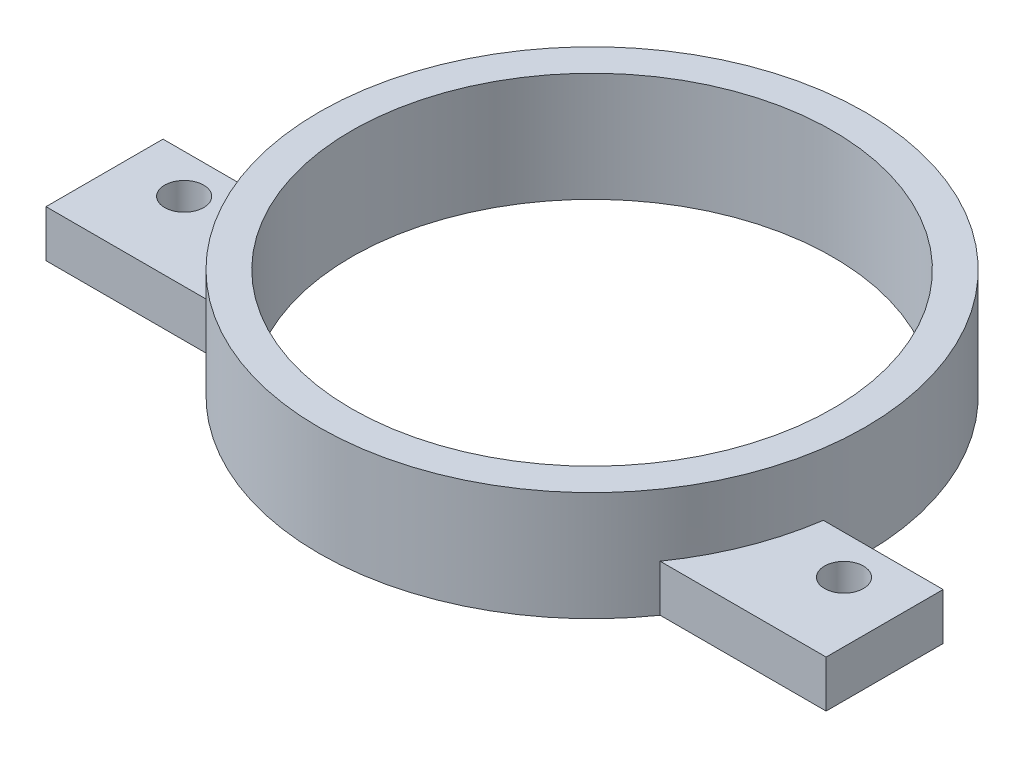
SolidWorks part; units mm, degrees
ref_plane "前视基准面" through (0, 0, 0) normal (0, 0, 1) x (1, 0, 0)
ref_plane "上视基准面" through (0, 0, 0) normal (0, 1, 0) x (1, 0, 0)
ref_plane "右视基准面" through (0, 0, 0) normal (1, 0, 0) x (0, 0, -1)
other "Configuration Table"
sketch "草图1" plane through (0, 0, 0) normal (0, 1, 0) x (1, 0, 0)
  line L0 (0, 0) -> (66.7277, 0) construction
  line L1 (35, 0) -> (55, 0)
  line L2 (55, 0) -> (55, -25)
  line L3 (55, -25) -> (24.4949, -25)
  line L4 (34.641, -5) -> (50, -5)
  line L5 (50, -5) -> (50, -20)
  line L6 (50, -20) -> (28.7228, -20)
  line L7 (0, 0) -> (0, 30.85) construction
  line L8 (-50, -20) -> (-28.7228, -20)
  line L9 (-50, -5) -> (-50, -20)
  line L10 (-34.641, -5) -> (-50, -5)
  line L11 (-55, -25) -> (-24.4949, -25)
  line L12 (-55, 0) -> (-55, -25)
  line L13 (-35, 0) -> (-55, 0)
  circle A0 centre (0, 0) radius 35
  circle A1 centre (42.2902, -10) radius 2.5
  circle A2 centre (0, 0) radius 30.85
  circle A3 centre (-42.2902, -10) radius 2.5
  dimension "D1" = 70
  dimension "D7" = 5
  dimension "D8" = 5
  dimension "D9" = 7.7098
  dimension "D10" = 61.7
  dimension "D2" = 25
  dimension "D3" = 20
  dimension "D4" = 5
  dimension "D5" = 5
  dimension "D6" = 5
extrude "凸台-拉伸1" add sketch "草图1" along normal blind 14 contours A2 A0 region at (33.9227, 0, 2.4355)
extrude "凸台-拉伸2" add sketch "草图1<3>" along normal blind 6 contours A0 L6 L5 L4 A1 region at (41.0003, 0, 13.1476)
sketch "草图1<3>" plane through (0, 0, 0) normal (0, 1, 0) x (1, 0, 0) same geometry as "草图1"
extrude "凸台-拉伸3" add sketch "草图1<4>" along normal blind 6 contours A0 L10 L9 L8 A3 region at (-41.0003, 0, 13.1476)
sketch "草图1<4>" plane through (0, 0, 0) normal (0, 1, 0) x (1, 0, 0) same geometry as "草图1"
